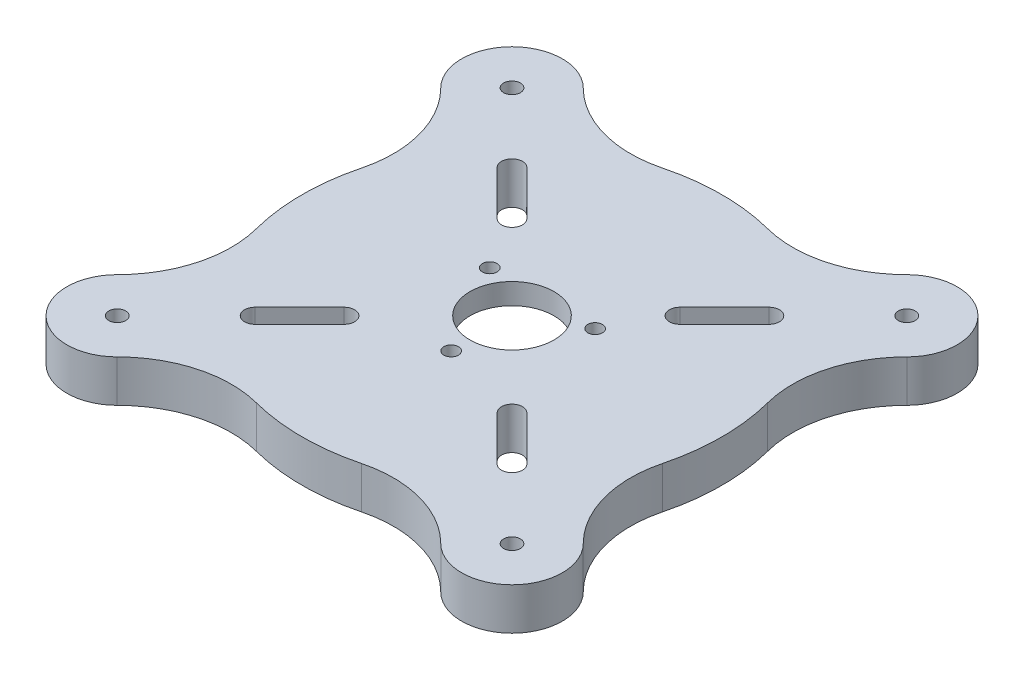
SolidWorks part; units mm, degrees
ref_plane "Front Plane" through (0, 0, 0) normal (0, 0, 1) x (1, 0, 0)
ref_plane "Top Plane" through (0, 0, 0) normal (0, 1, 0) x (1, 0, 0)
ref_plane "Right Plane" through (0, 0, 0) normal (1, 0, 0) x (0, 0, -1)
sketch "Sketch1" plane through (0, 0, 0) normal (0, 1, 0) x (1, 0, 0)
  line L0 (-47.0226, -47.0226) -> (47.0226, 47.0226) construction
  line L1 (-55.5079, -38.5373) -> (38.5373, 55.5079) construction
  line L2 (-38.5373, -55.5079) -> (55.5079, 38.5373) construction
  line L3 (0, 0) -> (0, 50) construction
  line L4 (47.0226, -47.0226) -> (-47.0226, 47.0226) construction
  line L5 (55.5079, -38.5373) -> (-38.5373, 55.5079) construction
  line L6 (38.5373, -55.5079) -> (-55.5079, 38.5373) construction
  line L7 (20, 20) -> (30.6066, 30.6066) construction
  line L8 (18.2322, 21.7678) -> (28.8388, 32.3744)
  line L9 (21.7678, 18.2322) -> (32.3744, 28.8388)
  line L10 (20, -20) -> (30.6066, -30.6066) construction
  line L11 (21.7678, -18.2322) -> (32.3744, -28.8388)
  line L12 (18.2322, -21.7678) -> (28.8388, -32.3744)
  line L13 (-20, -20) -> (-30.6066, -30.6066) construction
  line L14 (-18.2322, -21.7678) -> (-28.8388, -32.3744)
  line L15 (-21.7678, -18.2322) -> (-32.3744, -28.8388)
  line L16 (-20, 20) -> (-30.6066, 30.6066) construction
  line L17 (-21.7678, 18.2322) -> (-32.3744, 28.8388)
  line L18 (-18.2322, 21.7678) -> (-28.8388, 32.3744)
  circle A0 centre (0, 0) radius 50
  arc A1 (-55.5079, -38.5373) -> (-38.5373, -55.5079) centre (-47.0226, -47.0226) ccw construction
  arc A2 (55.5079, 38.5373) -> (38.5373, 55.5079) centre (47.0226, 47.0226) ccw construction
  arc A3 (55.5079, -38.5373) -> (38.5373, -55.5079) centre (47.0226, -47.0226) cw construction
  arc A4 (-55.5079, 38.5373) -> (-38.5373, 55.5079) centre (-47.0226, 47.0226) cw construction
  arc A5 (38.5373, 55.5079) -> (12.5104, 48.4096) centre (19.3129, 74.7323) cw
  arc A6 (55.5079, 38.5373) -> (48.4096, 12.5104) centre (74.7323, 19.3129) ccw
  arc A7 (18.2322, 21.7678) -> (21.7678, 18.2322) centre (20, 20) ccw
  arc A8 (32.3744, 28.8388) -> (28.8388, 32.3744) centre (30.6066, 30.6066) ccw
  circle A9 centre (47.0226, 47.0226) radius 2
  arc A10 (38.5373, 55.5079) -> (55.5079, 38.5373) centre (47.0226, 47.0226) cw
  arc A11 (55.5079, -38.5373) -> (38.5373, -55.5079) centre (47.0226, -47.0226) cw
  circle A12 centre (47.0226, -47.0226) radius 2
  arc A13 (38.5373, -55.5079) -> (12.5104, -48.4096) centre (19.3129, -74.7323) ccw
  arc A14 (55.5079, -38.5373) -> (48.4096, -12.5104) centre (74.7323, -19.3129) cw
  arc A15 (21.7678, -18.2322) -> (18.2322, -21.7678) centre (20, -20) ccw
  arc A16 (28.8388, -32.3744) -> (32.3744, -28.8388) centre (30.6066, -30.6066) ccw
  arc A17 (-38.5373, -55.5079) -> (-55.5079, -38.5373) centre (-47.0226, -47.0226) cw
  circle A18 centre (-47.0226, -47.0226) radius 2
  arc A19 (-55.5079, -38.5373) -> (-48.4096, -12.5104) centre (-74.7323, -19.3129) ccw
  arc A20 (-38.5373, -55.5079) -> (-12.5104, -48.4096) centre (-19.3129, -74.7323) cw
  arc A21 (-18.2322, -21.7678) -> (-21.7678, -18.2322) centre (-20, -20) ccw
  arc A22 (-32.3744, -28.8388) -> (-28.8388, -32.3744) centre (-30.6066, -30.6066) ccw
  arc A23 (-55.5079, 38.5373) -> (-38.5373, 55.5079) centre (-47.0226, 47.0226) cw
  circle A24 centre (-47.0226, 47.0226) radius 2
  arc A25 (-38.5373, 55.5079) -> (-12.5104, 48.4096) centre (-19.3129, 74.7323) ccw
  arc A26 (-55.5079, 38.5373) -> (-48.4096, 12.5104) centre (-74.7323, 19.3129) cw
  arc A27 (-21.7678, 18.2322) -> (-18.2322, 21.7678) centre (-20, 20) ccw
  arc A28 (-28.8388, 32.3744) -> (-32.3744, 28.8388) centre (-30.6066, 30.6066) ccw
  point P5 (0, 0)
  point P13 (0, 0)
  point P26 (25.3033, 25.3033)
  point P45 (25.3033, -25.3033)
  point P61 (-25.3033, -25.3033)
  point P77 (-25.3033, 25.3033)
  point P85 (0, 0)
  dimension "D1" = 100
  dimension "D2" = 12
  dimension "D5" = 2.5
  dimension "D8" = 4
  dimension "D3" = 133
  dimension "D4" = 45
  dimension "D6" = 15
  dimension "D7" = 20
  dimension "D9" = 4
extrude "Boss-Extrude1" add sketch "Sketch1" along normal blind 10 contours A17 A20 A0 A19 A18 | A11 A14 A0 A13 A12 | A10 A5 A0 A6 A9 | A23 A26 A0 A25 A24 | A0 A28 L18 A27 L17 A22 L15 A21 L14 A16 L12 A15 L11 A8 L9 A7 L8 region at (0, 0, 0) region at (43.2982, 0, -43.2982) region at (43.2982, 0, 43.2982) region at (-43.2982, 0, -43.2982) region at (-43.2982, 0, 43.2982)
sketch "Sketch2" plane through (0, 0, 0) normal (0, -1, 0) x (1, 0, 0)
  circle A0 centre (0, 0) radius 21.25
  circle A1 centre (0, 14.5) radius 1.75
  circle A2 centre (0, 0) radius 21.25
  circle A3 centre (12.5574, -7.25) radius 1.75
  circle A4 centre (0, 0) radius 21.25
  circle A5 centre (-12.5574, -7.25) radius 1.75
  point P14 (0, 0)
  dimension "D1" = 42.5
  dimension "D3" = 3.5
  dimension "D2" = 14.5
  dimension "D4" = 3
extrude "Cut-Extrude1" cut sketch "Sketch2" against normal blind 5 contours A0
extrude "Cut-Extrude2" cut sketch "Sketch2<3>" against normal through all contours A5 | A3 | A1 region at (12.5574, 0, -7.25) region at (-12.5574, 0, -7.25)
sketch "Sketch2<3>" plane through (0, 0, 0) normal (0, -1, 0) x (1, 0, 0) same geometry as "Sketch2"
sketch "Sketch4" plane through (0, 5, 0) normal (0, -1, 0) x (-1, 0, 0)
  circle A0 centre (0, 0) radius 10
  dimension "D1" = 20
extrude "Cut-Extrude3" cut sketch "Sketch4" along direction (0, -1, 0) on the side against the normal through all
